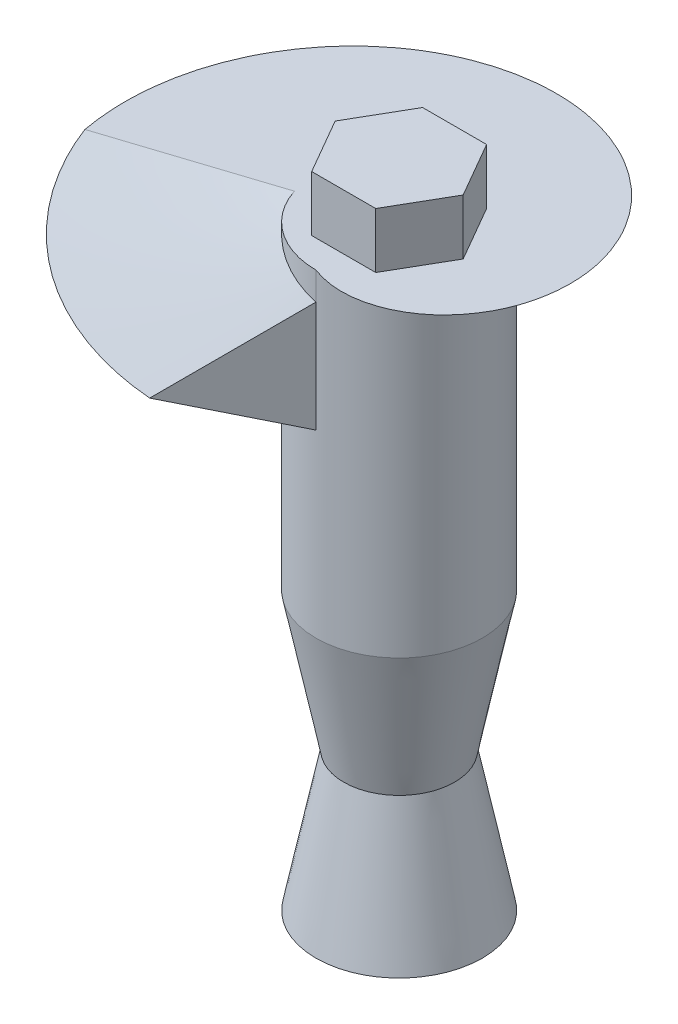
SolidWorks part; units mm, degrees
ref_plane "Front Plane" through (0, 0, 0) normal (0, 0, 1) x (1, 0, 0)
ref_plane "Top Plane" through (0, 0, 0) normal (0, 1, 0) x (1, 0, 0)
ref_plane "Right Plane" through (0, 0, 0) normal (1, 0, 0) x (0, 0, -1)
ref_plane "Plane1" through (0, 5, 0) normal (0, 1, 0) x (1, 0, 0)
sketch "Sketch3" plane through (0, 5, 0) normal (0, 1, 0) x (1, 0, 0)
  circle A0 centre (0, 0) radius 3
  dimension "D1" = 6
sketch "Sketch4" plane through (0, 0, 0) normal (0, 1, 0) x (1, 0, 0)
  circle A0 centre (0, 0) radius 2
  dimension "D1" = 4
loft "Loft2" add profiles "Sketch3", "Sketch4" connector at (0, 5, 3) connector at (0, 0, 2)
mirror "Mirror1" about plane through (0, 0, 0) normal (0, 1, 0) of "Loft2"
sketch "Sketch5" plane through (0, 5, 0) normal (0, 1, 0) x (1, 0, 0)
  circle A0 centre (0, 0) radius 3
  circle A1 centre (0, 0) radius 3 construction
extrude "Boss-Extrude1" add sketch "Sketch5" along normal blind 11.5
sketch "Sketch7" plane through (0, 16.5, 0) normal (0, 1, 0) x (1, 0, 0)
  circle A0 centre (0, 0) radius 3
  circle A1 centre (0, 0) radius 3 construction
curve "Helix/Spiral1" pitch 5 height 5 radius 3 left hand yes centre (0, 16.5, 0) axis (0, 1, 0) start towards (0, 0, 1)
sketch "Sketch9" plane through (0, 0, 0) normal (1, 0, 0) x (0, 0, -1)
  line L0 (-3, 11.5) -> (-9, 15.5)
  line L1 (-9, 15.5) -> (-3, 15.5)
  line L2 (-3, 16.5) -> (-3, 5) construction
  line L3 (-3, 15.5) -> (-3, 11.5)
  dimension "D1" = 6
  dimension "D2" = 4
  dimension "D3" = 6.5
sweep "Sweep1" add profiles "Sketch9" path "Helix/Spiral1"
sketch "Sketch10" plane through (0, 16.5, 0) normal (0, 1, 0) x (1, 0, 0)
  circle A0 centre (0, 0) radius 10
  dimension "D1" = 20
extrude "Cut-Extrude1" cut sketch "Sketch10" along normal through all
sketch "Sketch11" plane through (0, 16.5, 0) normal (0, 1, 0) x (1, 0, 0)
  line L1 (-2.3094, 0) -> (-1.1547, -2)
  line L2 (-1.1547, -2) -> (1.1547, -2)
  line L3 (1.1547, -2) -> (2.3094, 0)
  line L4 (2.3094, 0) -> (1.1547, 2)
  line L5 (1.1547, 2) -> (-1.1547, 2)
  line L6 (-1.1547, 2) -> (-2.3094, 0)
  circle A0 centre (0, 0) radius 2 construction
  dimension "D1" = 4
extrude "Boss-Extrude3" add sketch "Sketch11" along normal blind 2
